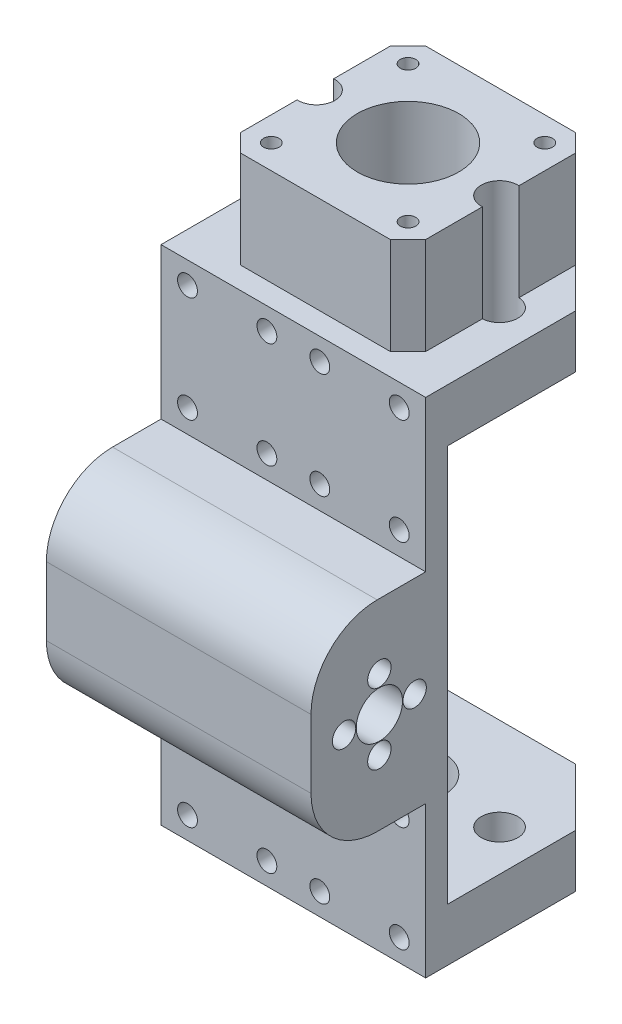
SolidWorks part; units mm, degrees
ref_plane "Front Plane" through (0, 0, 0) normal (0, 0, 1) x (1, 0, 0)
ref_plane "Top Plane" through (0, 0, 0) normal (0, 1, 0) x (1, 0, 0)
ref_plane "Right Plane" through (0, 0, 0) normal (1, 0, 0) x (0, 0, -1)
sketch "Sketch2" plane through (0, 0, 0) normal (1, 0, 0) x (0, 0, -1)
  line L5 (10.5, 57) -> (15.5, 57)
  line L6 (10.5, 57) -> (10.5, -57)
  line L7 (10.5, -57) -> (15.5, -57)
  line L8 (15.5, 57) -> (15.5, -57)
  line L13 (-15.5, -22.75) -> (15.5, -22.75)
  line L18 (-15.5, -22.75) -> (-15.5, 22.75)
  line L19 (-15.5, 22.75) -> (15.5, 22.75)
  line L20 (15.5, -22.75) -> (15.5, 22.75)
  line L21 (-15.5, -22.75) -> (15.5, 22.75) construction
  line L22 (-15.5, 22.75) -> (15.5, -22.75) construction
  circle A1 centre (0, 0) radius 5.25
  dimension "D1" = 57
  dimension "D8" = 10.5
  dimension "D2" = 57
  dimension "D3" = 10.5
  dimension "D4" = 5
  dimension "D5" = 45.5
extrude "Boss-Extrude1" add sketch "Sketch2" along normal blind 30 and the other way blind 30 contours L6 | L8 L5 L6 L7 | L6 L5 L8 L7 region at (0, 39.875, -13) region at (0, 0, -9.976)
sketch "Sketch3" plane through (-30, 0, 0) normal (1, 0, 0) x (0, 0, -1)
  circle A0 centre (0, 0) radius 11.5
  dimension "D1" = 23
extrude "Cut-Extrude2" cut sketch "Sketch3" along normal blind 30
sketch "Sketch5" plane through (30, 0, 0) normal (1, 0, 0) x (0, 0, -1)
  line L0 (0, 0) -> (0, 22.75) construction
  line L1 (-15.5, 22.75) -> (10.5, 22.75) construction
  circle A0 centre (0, 8) radius 1.75
  circle A1 centre (8, 0) radius 1.75
  circle A2 centre (0, -8) radius 1.75
  circle A3 centre (-8, 0) radius 1.75
  point P16 (0, 0)
  dimension "D1" = 3.5
  dimension "D2" = 8
  dimension "D4" = 8
  dimension "D5" = 8
  dimension "D3" = 4
extrude "Cut-Extrude3" cut sketch "Sketch5" against normal up to next
fillet "Fillet1" radius 15 2 edges at (0, -22.75, 15.5) (0, 22.75, 15.5)
sketch "Sketch6" plane through (0, 0, -15.5) normal (0, 0, -1) x (-1, 0, 0)
  line L0 (0, 57) -> (0, -57) construction
  line L1 (-30, 57) -> (30, 57) construction
  line L2 (-30, -57) -> (30, -57) construction
  line L3 (-30, 0) -> (30, 0) construction
  line L4 (-30, 57) -> (-30, -57) construction
  line L5 (30, 57) -> (30, -57) construction
  circle A0 centre (-24, 52) radius 2.25
  circle A1 centre (-6, 52) radius 2.25
  circle A2 centre (-24, 28) radius 2.25
  circle A3 centre (-6, 28) radius 2.25
  circle A4 centre (6, 28) radius 2.25
  circle A5 centre (24, 28) radius 2.25
  circle A6 centre (6, 52) radius 2.25
  circle A7 centre (24, 52) radius 2.25
  circle A8 centre (24, -52) radius 2.25
  circle A9 centre (6, -52) radius 2.25
  circle A10 centre (24, -28) radius 2.25
  circle A11 centre (6, -28) radius 2.25
  circle A12 centre (-6, -28) radius 2.25
  circle A13 centre (-24, -28) radius 2.25
  circle A14 centre (-6, -52) radius 2.25
  circle A15 centre (-24, -52) radius 2.25
  dimension "D1" = 4.5
  dimension "D2" = 5
  dimension "D3" = 6
  dimension "D5" = 18
  dimension "D7" = 24
  dimension "D4" = 2
  dimension "D6" = 2
extrude "Cut-Extrude4" cut sketch "Sketch6" against normal up to next
sketch "Sketch7" plane through (0, 0, -15.5) normal (0, 0, -1) x (-1, 0, 0)
  line L0 (30, 57) -> (30, -57) construction
  line L1 (-30, 57) -> (30, 57)
  line L2 (-30, 57) -> (-30, 45)
  line L3 (-30, 45) -> (30, 45)
  line L4 (30, 57) -> (30, 45)
  line L5 (-30, 0) -> (30, 0) construction
  line L6 (-30, 57) -> (-30, -57) construction
  line L7 (-30, -45) -> (30, -45)
  line L8 (30, -57) -> (30, -45)
  line L9 (-30, -57) -> (30, -57)
  line L10 (-30, -57) -> (-30, -45)
  dimension "D1" = 12
extrude "Boss-Extrude2" add sketch "Sketch7" along normal blind 42
sketch "Sketch18" plane through (0, 57, 0) normal (0, 1, 0) x (1, 0, 0)
  line L0 (0, 57.5) -> (0, 10.5) construction
  line L1 (-30, 57.5) -> (30, 57.5) construction
  line L2 (-30, 10.5) -> (30, 10.5) construction
  line L4 (-21, 15.5) -> (21, 15.5)
  line L5 (-21, 15.5) -> (-21, 57.5)
  line L6 (-21, 57.5) -> (21, 57.5)
  line L7 (21, 15.5) -> (21, 57.5)
  line L8 (-21, 15.5) -> (21, 57.5) construction
  line L9 (-21, 57.5) -> (21, 15.5) construction
  point P6 (0, 36.5)
  dimension "D1" = 42
  dimension "D2" = 42
sketch "Sketch8" plane through (0, 57, 0) normal (0, 1, 0) x (1, 0, 0)
  line L0 (0, 57.5) -> (0, 10.5) construction
  line L1 (-30, 57.5) -> (30, 57.5) construction
  line L2 (-30, 10.5) -> (30, 10.5) construction
  line L3 (-11.5, 36.5) -> (-30, 36.5) construction
  line L5 (-30, 10.5) -> (-30, 57.5) construction
  circle A0 centre (0, 36.5) radius 11.5
  circle A1 centre (-15.5, 52) radius 1.75
  circle A2 centre (15.5, 52) radius 1.75
  circle A3 centre (15.5, 21) radius 1.75
  circle A4 centre (-15.5, 21) radius 1.75
  circle A5 centre (-20.75, 36.5) radius 4.15
  circle A6 centre (20.75, 36.5) radius 4.15
  dimension "D1" = 23
  dimension "D2" = 21
  dimension "D3" = 15.5
  dimension "D4" = 15.5
  dimension "D5" = 3.5
  dimension "D6" = 8.3
extrude "Boss-Extrude5" add sketch "Sketch18" along normal blind 22
extrude "Cut-Extrude5" cut sketch "Sketch8" against normal up to next from offset 22
sketch "Sketch9" plane through (0, -45, 0) normal (0, 1, 0) x (1, 0, 0)
  line L0 (30, 36.5) -> (-30, 36.5) construction
  line L1 (30, 57.5) -> (30, 15.5) construction
  line L2 (-30, 57.5) -> (-30, 15.5) construction
  line L3 (0, 57.5) -> (0, 15.5) construction
  line L4 (-30, 57.5) -> (30, 57.5) construction
  line L5 (-30, 15.5) -> (30, 15.5) construction
  circle A0 centre (-20.75, 36.5) radius 4.15
  circle A1 centre (20.75, 36.5) radius 4.15
  circle A2 centre (0, 36.5) radius 8.15
  dimension "D1" = 8.3
  dimension "D2" = 20.75
  dimension "D3" = 16.3
extrude "Cut-Extrude6" cut sketch "Sketch9" against normal blind 10
sketch "Sketch10" plane through (0, -55, 0) normal (0, 1, 0) x (1, 0, 0)
  circle A0 centre (0, 36.5) radius 4.15
  dimension "D1" = 8.3
extrude "Cut-Extrude7" cut sketch "Sketch10" against normal up to next
sketch "Sketch11" plane through (0, 45, 0) normal (0, -1, 0) x (1, 0, 0)
  line L0 (0, -15.5) -> (0, -57.5) construction
  line L1 (30, -15.5) -> (-30, -15.5) construction
  line L2 (30, -57.5) -> (-30, -57.5) construction
  line L3 (20.75, -36.5) -> (-20.75, -36.5) construction
  circle A0 centre (15.5, -52) radius 3
  circle A1 centre (-15.5, -52) radius 3
  circle A2 centre (-15.5, -21) radius 3
  circle A3 centre (15.5, -21) radius 3
  dimension "D1" = 6
extrude "Cut-Extrude8" cut sketch "Sketch11" against normal blind 6
sketch "Sketch14" plane through (30, 0, 0) normal (1, 0, 0) x (0, 0, -1)
  circle A0 centre (0, 8) radius 2.65
  circle A1 centre (8, 0) radius 2.65
  circle A2 centre (0, -8) radius 2.65
  circle A3 centre (-8, 0) radius 2.65
  point P12 (0, 0)
  dimension "D1" = 5.3
  dimension "D3" = 8
  dimension "D4" = 8
  dimension "D2" = 4
extrude "Cut-Extrude10" cut sketch "Sketch14" against normal blind 5.3
chamfer "Chamfer3" distance 13 angle 45 4 edges at (30, 51, -57.5) (-30, 51, -57.5) (-30, -51, -57.5) (30, -51, -57.5)
chamfer "Chamfer4" distance 4 angle 45 2 edges at (21, 68, -15.5) (-21, 68, -15.5)
